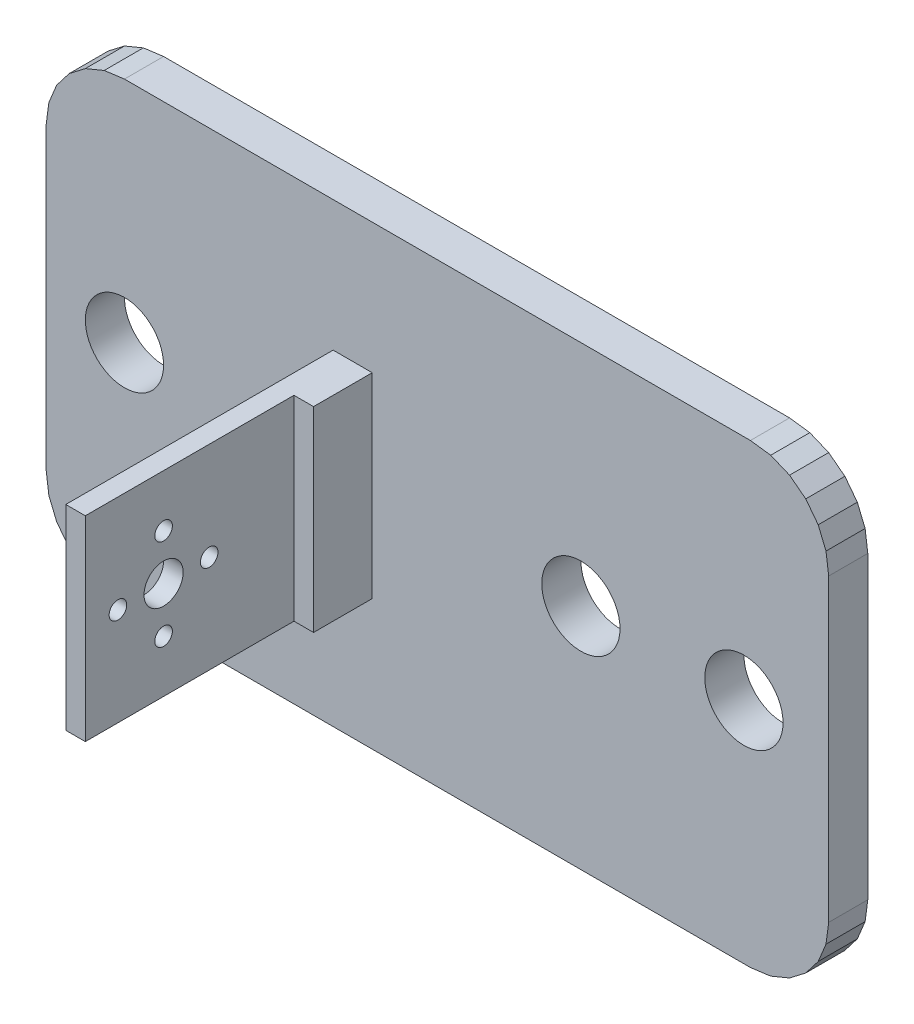
SolidWorks part; units mm, degrees
ref_plane "Front Plane" through (0, 0, 0) normal (0, 0, 1) x (1, 0, 0)
ref_plane "Top Plane" through (0, 0, 0) normal (0, 1, 0) x (1, 0, 0)
ref_plane "Right Plane" through (0, 0, 0) normal (1, 0, 0) x (0, 0, -1)
ref_plane "PZ_m35_000" through (0, 0, -35) normal (0, 0, 1) x (1, 0, 0)
sketch "S_box1" plane through (0, 0, -35) normal (0, 0, 1) x (1, 0, 0)
  line L0 (-62, -35) -> (58, -35)
  line L1 (58, -35) -> (58, 35)
  line L2 (58, 35) -> (-62, 35)
  line L3 (-62, 35) -> (-62, -35)
  dimension "P1" = 62
  dimension "P2" = 35
  dimension "P3" = 58
  dimension "P4" = 35
  dimension "P5" = 58
  dimension "P6" = 35
  dimension "P7" = 62
  dimension "P8" = 35
extrude "Boss_1" add sketch "S_box1" along normal blind 6
ref_plane "PZ_m29_500" through (0, 0, -29.5) normal (0, 0, 1) x (1, 0, 0)
sketch "S_box2" plane through (0, 0, -29.5) normal (0, 0, 1) x (1, 0, 0)
  line L0 (-18, -15) -> (-15, -15)
  line L1 (-15, -15) -> (-15, 15)
  line L2 (-15, 15) -> (-18, 15)
  line L3 (-18, 15) -> (-18, -15)
  dimension "P1" = 18
  dimension "P2" = 15
  dimension "P3" = 15
  dimension "P4" = 15
  dimension "P5" = 15
  dimension "P6" = 15
  dimension "P7" = 18
  dimension "P8" = 15
extrude "Boss_2" add sketch "S_box2" along normal blind 41.5
sketch "S_box3" plane through (0, 0, -29.5) normal (0, 0, 1) x (1, 0, 0)
  line L0 (-15.5, -15) -> (-12, -15)
  line L1 (-12, -15) -> (-12, 15)
  line L2 (-12, 15) -> (-15.5, 15)
  line L3 (-15.5, 15) -> (-15.5, -15)
  dimension "P1" = 15.5
  dimension "P2" = 15
  dimension "P3" = 12
  dimension "P4" = 15
  dimension "P5" = 12
  dimension "P6" = 15
  dimension "P7" = 15.5
  dimension "P8" = 15
extrude "Boss_3" add sketch "S_box3" along normal blind 9.5
ref_plane "PX_m18_100" through (-18.1, 0, 0) normal (1, 0, 0) x (0, 0, -1)
sketch "S_hole4" plane through (-18.1, 0, 0) normal (1, 0, 0) x (0, 0, -1)
  circle A0 centre (0, 0) radius 3
  dimension "D1_S_hole4" = 6
extrude "Hole_4" cut sketch "S_hole4" along normal blind 3.2
sketch "S_hole5" plane through (-18.1, 0, 0) normal (1, 0, 0) x (0, 0, -1)
  circle A0 centre (0, 7) radius 1.35
  dimension "D1_S_hole5" = 2.7
  dimension "P2" = 7
extrude "Hole_5" cut sketch "S_hole5" along normal blind 3.2
sketch "S_hole6" plane through (-18.1, 0, 0) normal (1, 0, 0) x (0, 0, -1)
  circle A0 centre (-7, 0) radius 1.35
  dimension "D1_S_hole6" = 2.7
  dimension "P2" = 7
extrude "Hole_6" cut sketch "S_hole6" along normal blind 3.2
sketch "S_hole7" plane through (-18.1, 0, 0) normal (1, 0, 0) x (0, 0, -1)
  circle A0 centre (0, -7) radius 1.35
  dimension "D1_S_hole7" = 2.7
  dimension "P2" = 7
extrude "Hole_7" cut sketch "S_hole7" along normal blind 3.2
sketch "S_hole8" plane through (-18.1, 0, 0) normal (1, 0, 0) x (0, 0, -1)
  circle A0 centre (7, 0) radius 1.35
  dimension "D1_S_hole8" = 2.7
  dimension "P2" = 7
extrude "Hole_8" cut sketch "S_hole8" along normal blind 3.2
ref_plane "PZ_m35_100" through (0, 0, -35.1) normal (0, 0, 1) x (1, 0, 0)
sketch "S_hole9" plane through (0, 0, -35.1) normal (0, 0, 1) x (1, 0, 0)
  circle A0 centre (-50, 0) radius 6
  dimension "D1_S_hole9" = 12
  dimension "P2" = 50
extrude "Hole_9" cut sketch "S_hole9" along normal blind 6.2
sketch "S_hole10" plane through (0, 0, -35.1) normal (0, 0, 1) x (1, 0, 0)
  circle A0 centre (-20, 0) radius 6
  dimension "D1_S_hole10" = 12
  dimension "P2" = 20
extrude "Hole_10" cut sketch "S_hole10" along normal blind 6.2
sketch "S_hole11" plane through (0, 0, -35.1) normal (0, 0, 1) x (1, 0, 0)
  circle A0 centre (20, 0) radius 6
  dimension "D1_S_hole11" = 12
  dimension "P2" = 20
extrude "Hole_11" cut sketch "S_hole11" along normal blind 6.2
sketch "S_hole12" plane through (0, 0, -35.1) normal (0, 0, 1) x (1, 0, 0)
  circle A0 centre (45, 0) radius 6
  dimension "D1_S_hole12" = 12
  dimension "P2" = 45
extrude "Hole_12" cut sketch "S_hole12" along normal blind 6.2
sketch "S_pcut13" plane through (0, 0, -35.1) normal (0, 0, 1) x (1, 0, 0)
  line L0 (58.6, 35.6) -> (46, 35.6)
  line L1 (46, 35.6) -> (46, 35)
  line L2 (46, 35) -> (49.106, 34.591)
  line L3 (49.106, 34.591) -> (52, 33.392)
  line L4 (52, 33.392) -> (54.485, 31.485)
  line L5 (54.485, 31.485) -> (56.392, 29)
  line L6 (56.392, 29) -> (57.591, 26.106)
  line L7 (57.591, 26.106) -> (58, 23)
  line L8 (58, 23) -> (58.6, 23)
  line L9 (58.6, 23) -> (58.6, 35.6)
  dimension "P1" = 58.6
  dimension "P2" = 35.6
  dimension "P3" = 46
  dimension "P4" = 35.6
  dimension "P5" = 46
  dimension "P6" = 35
  dimension "P7" = 49.106
  dimension "P8" = 34.591
  dimension "P9" = 52
  dimension "P10" = 33.392
  dimension "P11" = 54.485
  dimension "P12" = 31.485
  dimension "P13" = 56.392
  dimension "P14" = 29
  dimension "P15" = 57.591
  dimension "P16" = 26.106
  dimension "P17" = 58
  dimension "P18" = 23
  dimension "P19" = 58.6
  dimension "P20" = 23
extrude "Cut_13" cut sketch "S_pcut13" along normal blind 6.2
sketch "S_pcut14" plane through (0, 0, -35.1) normal (0, 0, 1) x (1, 0, 0)
  line L0 (58.6, -35.6) -> (46, -35.6)
  line L1 (46, -35.6) -> (46, -35)
  line L2 (46, -35) -> (49.106, -34.591)
  line L3 (49.106, -34.591) -> (52, -33.392)
  line L4 (52, -33.392) -> (54.485, -31.485)
  line L5 (54.485, -31.485) -> (56.392, -29)
  line L6 (56.392, -29) -> (57.591, -26.106)
  line L7 (57.591, -26.106) -> (58, -23)
  line L8 (58, -23) -> (58.6, -23)
  line L9 (58.6, -23) -> (58.6, -35.6)
  dimension "P1" = 58.6
  dimension "P2" = 35.6
  dimension "P3" = 46
  dimension "P4" = 35.6
  dimension "P5" = 46
  dimension "P6" = 35
  dimension "P7" = 49.106
  dimension "P8" = 34.591
  dimension "P9" = 52
  dimension "P10" = 33.392
  dimension "P11" = 54.485
  dimension "P12" = 31.485
  dimension "P13" = 56.392
  dimension "P14" = 29
  dimension "P15" = 57.591
  dimension "P16" = 26.106
  dimension "P17" = 58
  dimension "P18" = 23
  dimension "P19" = 58.6
  dimension "P20" = 23
extrude "Cut_14" cut sketch "S_pcut14" along normal blind 6.2
sketch "S_pcut15" plane through (0, 0, -35.1) normal (0, 0, 1) x (1, 0, 0)
  line L0 (-62.6, 35.6) -> (-50, 35.6)
  line L1 (-50, 35.6) -> (-50, 35)
  line L2 (-50, 35) -> (-53.106, 34.591)
  line L3 (-53.106, 34.591) -> (-56, 33.392)
  line L4 (-56, 33.392) -> (-58.485, 31.485)
  line L5 (-58.485, 31.485) -> (-60.392, 29)
  line L6 (-60.392, 29) -> (-61.591, 26.106)
  line L7 (-61.591, 26.106) -> (-62, 23)
  line L8 (-62, 23) -> (-62.6, 23)
  line L9 (-62.6, 23) -> (-62.6, 35.6)
  dimension "P1" = 62.6
  dimension "P2" = 35.6
  dimension "P3" = 50
  dimension "P4" = 35.6
  dimension "P5" = 50
  dimension "P6" = 35
  dimension "P7" = 53.106
  dimension "P8" = 34.591
  dimension "P9" = 56
  dimension "P10" = 33.392
  dimension "P11" = 58.485
  dimension "P12" = 31.485
  dimension "P13" = 60.392
  dimension "P14" = 29
  dimension "P15" = 61.591
  dimension "P16" = 26.106
  dimension "P17" = 62
  dimension "P18" = 23
  dimension "P19" = 62.6
  dimension "P20" = 23
extrude "Cut_15" cut sketch "S_pcut15" along normal blind 6.2
sketch "S_pcut16" plane through (0, 0, -35.1) normal (0, 0, 1) x (1, 0, 0)
  line L0 (-62.6, -35.6) -> (-50, -35.6)
  line L1 (-50, -35.6) -> (-50, -35)
  line L2 (-50, -35) -> (-53.106, -34.591)
  line L3 (-53.106, -34.591) -> (-56, -33.392)
  line L4 (-56, -33.392) -> (-58.485, -31.485)
  line L5 (-58.485, -31.485) -> (-60.392, -29)
  line L6 (-60.392, -29) -> (-61.591, -26.106)
  line L7 (-61.591, -26.106) -> (-62, -23)
  line L8 (-62, -23) -> (-62.6, -23)
  line L9 (-62.6, -23) -> (-62.6, -35.6)
  dimension "P1" = 62.6
  dimension "P2" = 35.6
  dimension "P3" = 50
  dimension "P4" = 35.6
  dimension "P5" = 50
  dimension "P6" = 35
  dimension "P7" = 53.106
  dimension "P8" = 34.591
  dimension "P9" = 56
  dimension "P10" = 33.392
  dimension "P11" = 58.485
  dimension "P12" = 31.485
  dimension "P13" = 60.392
  dimension "P14" = 29
  dimension "P15" = 61.591
  dimension "P16" = 26.106
  dimension "P17" = 62
  dimension "P18" = 23
  dimension "P19" = 62.6
  dimension "P20" = 23
extrude "Cut_16" cut sketch "S_pcut16" along normal blind 6.2
equation "\"plate_t\" = 3"
equation "\"clearance\" = 0.4"
